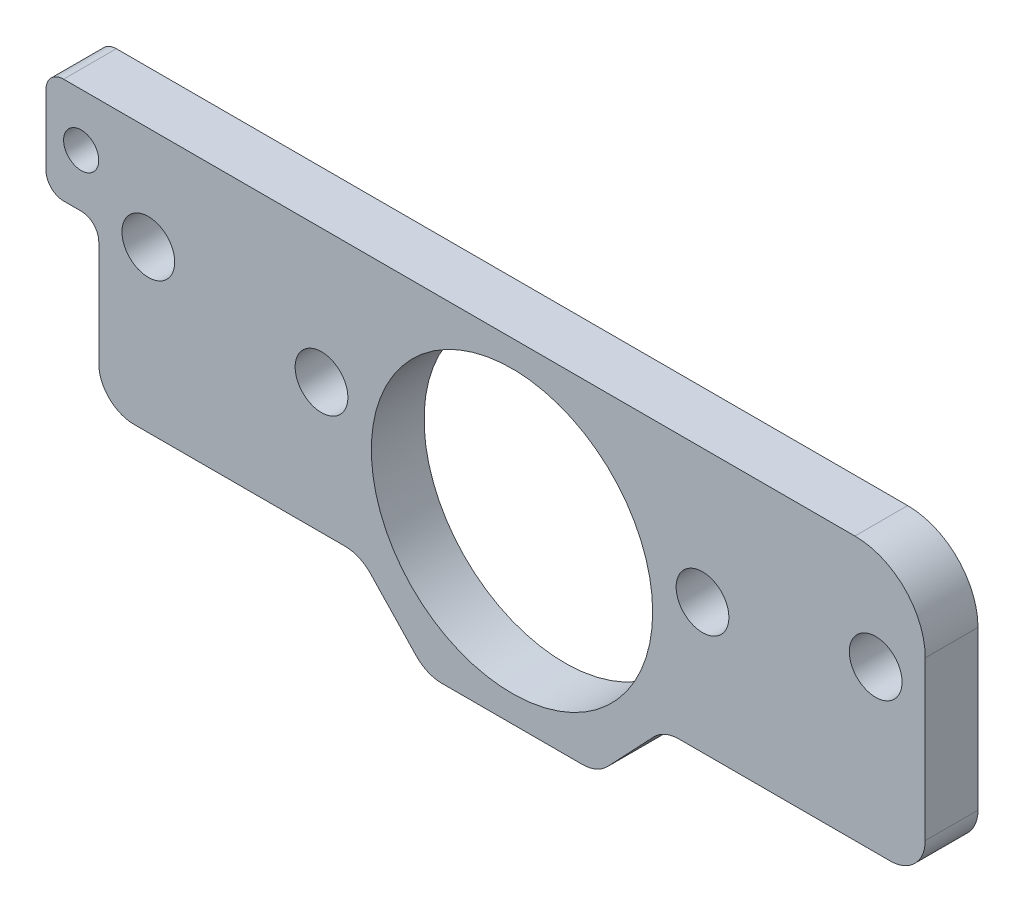
SolidWorks part; units mm, degrees
ref_plane "Front" through (0, 0, 0) normal (0, 0, 1) x (1, 0, 0)
ref_plane "Top" through (0, 0, 0) normal (0, 1, 0) x (1, 0, 0)
ref_plane "Right" through (0, 0, 0) normal (1, 0, 0) x (0, 0, -1)
sketch "Эскиз1" plane through (0, 0, 0) normal (0, 0, 1) x (1, 0, 0)
  line L0 (-2.5263, 8.6597) -> (-2.5263, -10.3403) construction
  line L1 (-6.5184, -10.3403) -> (1.4657, -10.3403)
  line L3 (-22.0263, 8.6597) -> (16.9737, 8.6597)
  line L5 (-26.0263, -4.3403) -> (-26.0263, 1.6597)
  line L6 (20.9737, 4.6597) -> (20.9737, -4.3403)
  line L7 (-2.5263, -0.8403) -> (-23.2073, 2.8063) construction
  line L8 (-22.0263, 8.6597) -> (-28.0263, 8.6597)
  line L9 (-29.0263, 7.6597) -> (-29.0263, 3.6597)
  line L10 (-28.0263, 2.6597) -> (-27.0263, 2.6597)
  line L11 (-24.0263, -6.3403) -> (-12.0263, -6.3403)
  line L12 (-10.5739, -6.9654) -> (-7.9708, -9.7153)
  line L13 (5.5212, -6.9654) -> (2.9181, -9.7153)
  line L14 (18.9737, -6.3403) -> (6.9737, -6.3403)
  circle A0 centre (-2.5263, -0.8403) radius 8
  arc A4 (16.9737, 8.6597) -> (20.9737, 4.6597) centre (16.9737, 4.6597) cw
  circle A5 centre (-23.2073, 2.8063) radius 1.5
  circle A6 centre (-13.3592, 1.0698) radius 1.5
  circle A7 centre (8.3066, 1.0698) radius 1.5
  circle A8 centre (18.1546, 2.8063) radius 1.5
  arc A9 (-26.0263, 1.6597) -> (-27.0263, 2.6597) centre (-27.0263, 1.6597) ccw
  arc A10 (-28.0263, 8.6597) -> (-29.0263, 7.6597) centre (-28.0263, 7.6597) ccw
  arc A11 (-29.0263, 3.6597) -> (-28.0263, 2.6597) centre (-28.0263, 3.6597) ccw
  circle A12 centre (-27.0263, 5.6597) radius 1
  arc A13 (20.9737, -4.3403) -> (18.9737, -6.3403) centre (18.9737, -4.3403) cw
  arc A14 (5.5212, -6.9654) -> (6.9737, -6.3403) centre (6.9737, -8.3403) cw
  arc A15 (2.9181, -9.7153) -> (1.4657, -10.3403) centre (1.4657, -8.3403) cw
  arc A16 (-7.9708, -9.7153) -> (-6.5184, -10.3403) centre (-6.5184, -8.3403) ccw
  arc A17 (-12.0263, -6.3403) -> (-10.5739, -6.9654) centre (-12.0263, -8.3403) cw
  arc A18 (-26.0263, -4.3403) -> (-24.0263, -6.3403) centre (-24.0263, -4.3403) ccw
  point P9 (20.9737, -6.3403)
  point P11 (20.9737, -10.3403)
  point P14 (-26.0263, -10.3403)
  point P17 (-26.0263, 8.6597)
  point P20 (20.9737, 8.6597)
  point P41 (-27.5263, 2.6597)
  point P43 (6.1129, -6.3403)
  point P46 (2.3264, -10.3403)
  point P49 (-7.3791, -10.3403)
  point P52 (-11.1656, -6.3403)
  point P55 (-26.0263, -6.3403)
  dimension "D1" = 16
  dimension "D4" = 14
  dimension "D5" = 10
  dimension "D10" = 1
  dimension "D11" = 3
  dimension "D2" = 2
  dimension "D3" = 47
  dimension "D6" = 9.5
  dimension "D7" = 80
  dimension "D8" = 11
  dimension "D9" = 19
  dimension "D12" = 2
  dimension "D14" = 3
  dimension "D15" = 6
extrude "Бобышка-Вытянуть1" add sketch "Эскиз1" along normal blind 3
